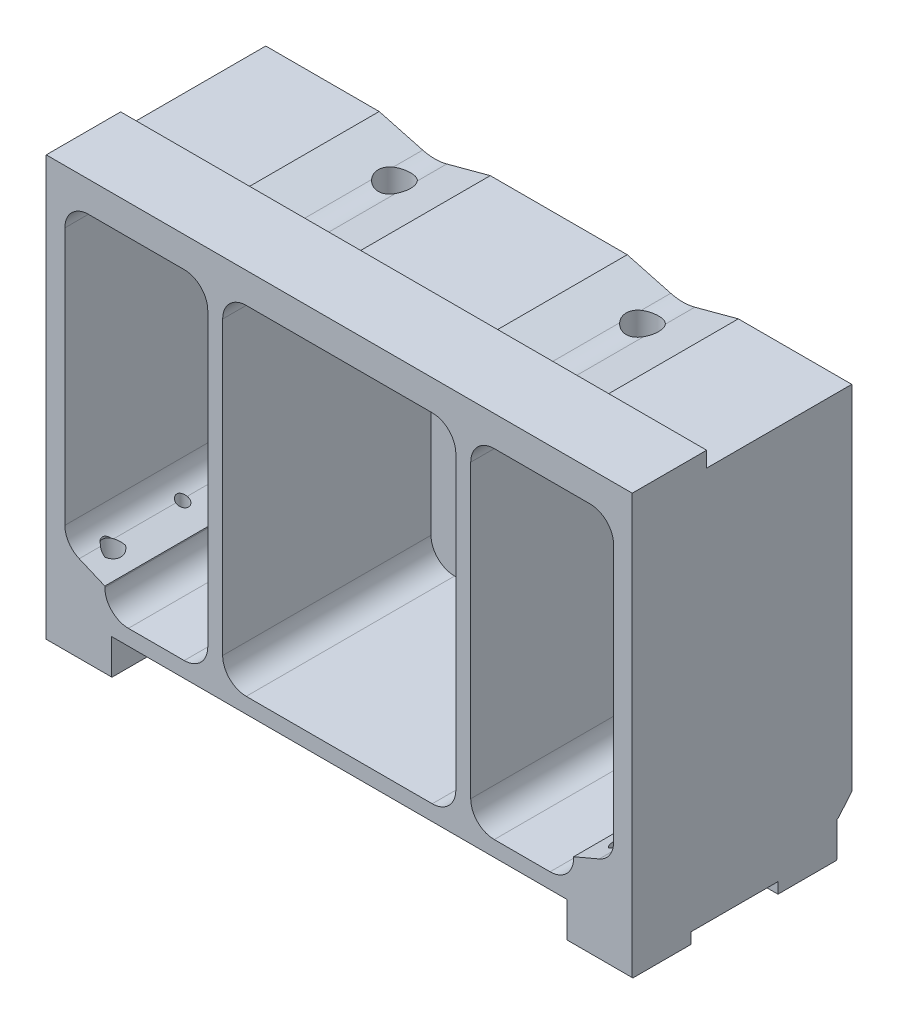
SolidWorks part; units mm, degrees
material "Invar 36"
ref_plane "Front Plane" through (0, 0, 0) normal (0, 0, 1) x (1, 0, 0)
ref_plane "Top Plane" through (0, 0, 0) normal (0, 1, 0) x (1, 0, 0)
ref_plane "Right Plane" through (0, 0, 0) normal (1, 0, 0) x (0, 0, -1)
sketch "Sketch1" plane through (0, 0, 0) normal (0, 0, 1) x (1, 0, 0)
  line L0 (-60.0075, 0) -> (60.0075, 0)
  line L1 (60.0075, 0) -> (60.0075, 82.8802)
  line L2 (60.0075, 82.8802) -> (-60.0075, 82.8802)
  line L4 (-60.0075, 82.8802) -> (-60.0075, 0)
  dimension "D1" = 120.015
  dimension "D2" = 82.8802
extrude "Boss-Extrude1" add sketch "Sketch1" along normal mid plane 41.91
sketch "Sketch3" plane through (0, 0, 0) normal (0, -1, 0) x (1, 0, 0)
  line L0 (-53.0225, -15.24) -> (53.0225, 15.24) construction
  line L1 (-53.0225, 15.24) -> (53.0225, 15.24) construction
  line L2 (-53.0225, 15.24) -> (-53.0225, -15.24) construction
  line L3 (-53.0225, -15.24) -> (53.0225, -15.24) construction
  line L4 (53.0225, 15.24) -> (53.0225, -15.24) construction
  circle A0 centre (-53.0225, 15.24) radius 1.5875
  circle A1 centre (53.0225, 15.24) radius 1.5875
  circle A2 centre (53.0225, -15.24) radius 1.5875
  circle A3 centre (-53.0225, -15.24) radius 1.5875
  dimension "D3" = 3.175
  dimension "D1" = 106.045
  dimension "D2" = 30.48
extrude "Cut-Extrude2" cut sketch "Sketch3" against normal blind 2.54
hole_wizard "Tapped Hole for #10-32 Helicoil1" positions "Sketch4" profile "Sketch5" tap size "#10-32" standard "Helicoil® Inch"
sketch "Sketch4" plane through (0, 0, 0) normal (0, -1, 0) x (1, 0, 0)
  point P0 (-53.0225, 15.24)
  point P3 (-53.0225, -15.24)
  point P6 (53.0225, 15.24)
  point P9 (53.0225, -15.24)
cosmetic thread "Hole Thread1" parameters "D1"=11.5316, "D2"=5.936
cosmetic thread "Hole Thread2" parameters "D1"=11.5316, "D2"=5.936
cosmetic thread "Hole Thread3" parameters "D1"=11.5316, "D2"=5.936
cosmetic thread "Hole Thread4" parameters "D1"=11.5316, "D2"=5.936
sketch "Sketch5" plane through (-53.0225, 0, 15.24) normal (1, 0, 0) x (0, 0, -1)
  line L0 (0, 0) -> (0, 18.628)
  line L1 (0, 18.628) -> (2.5527, 17.0942)
  line L2 (2.5527, 17.0942) -> (2.5527, 0)
  line L5 (2.5527, 0) -> (0, 0)
  line L10 (0, 18.628) -> (-2.5527, 17.0942) construction
  line L11 (0, -6.35) -> (0, 107.95) construction
  dimension "Tap Drill Dia." = 5.1054
  dimension "Tap Drill Depth" = 17.0942
  dimension "Drill Angle" = 118
chamfer "Chamfer1" distance 0.127 angle 45 2 edges at (0, 0, -20.955) (0, 0, 20.955)
sketch "Sketch6" plane through (0, 0, 0) normal (0, -1, 0) x (1, 0, 0)
  line L0 (-60.0075, 20.955) -> (60.0075, 20.955) construction
  line L1 (-46.6725, 20.955) -> (46.6725, 20.955)
  line L2 (-46.6725, 20.955) -> (-46.6725, 8.89)
  line L3 (-46.6725, -20.955) -> (46.6725, -20.955)
  line L4 (46.6725, 20.955) -> (46.6725, 8.89)
  line L5 (60.0075, -20.955) -> (-60.0075, -20.955) construction
  line L6 (-60.0075, 20.828) -> (-60.0075, -20.828) construction
  line L7 (-60.0075, 8.89) -> (-46.6725, 8.89)
  line L8 (-60.0075, 8.89) -> (-60.0075, -8.89)
  line L9 (-60.0075, -8.89) -> (-46.6725, -8.89)
  line L10 (60.0075, 8.89) -> (60.0075, -8.89)
  line L11 (60.0075, 20.828) -> (60.0075, -20.828) construction
  line L12 (-46.6725, -8.89) -> (-46.6725, -20.955)
  line L13 (46.6725, 8.89) -> (60.0075, 8.89)
  line L14 (46.6725, -8.89) -> (60.0075, -8.89)
  line L15 (46.6725, -8.89) -> (46.6725, -20.955)
  circle A0 centre (-53.0225, 15.24) radius 2.5527 construction
  circle A1 centre (53.0225, 15.24) radius 2.5527 construction
  circle A2 centre (-53.0225, -15.24) radius 2.5527 construction
  dimension "D1" = 6.35
  dimension "D3" = 6.35
  dimension "D2" = 6.35
  dimension "D4" = 6.35
extrude "Cut-Extrude3" cut sketch "Sketch6" against normal blind 7.3152
sketch "Sketch7" plane through (0, 7.3152, 0) normal (0, -1, 0) x (1, 0, 0)
  line L0 (-53.0225, 15.24) -> (-53.0225, -15.24) construction
  line L2 (53.0225, 15.24) -> (53.0225, -15.24) construction
  line L4 (-53.0225, 0) -> (53.0225, 0) construction
  circle A0 centre (-53.0225, 0) radius 1.585
  circle A4 centre (53.0225, 0) radius 1.585
  dimension "D1" = 3.1699
extrude "Cut-Extrude4" cut sketch "Sketch7" against normal blind 6.35
sketch "Sketch8" plane through (0, 0, -20.955) normal (0, 0, -1) x (-1, 0, 0)
  line L0 (60.0075, 82.8802) -> (60.0075, 0.127) construction
  line L1 (-60.0075, 82.8802) -> (60.0075, 82.8802)
  line L2 (-60.0075, 82.8802) -> (-60.0075, 7.3152)
  line L3 (-60.0075, 7.3152) -> (60.0075, 7.3152)
  line L4 (60.0075, 82.8802) -> (60.0075, 7.3152)
  line L5 (46.6725, 7.3152) -> (-46.6725, 7.3152) construction
extrude "Boss-Extrude2" add sketch "Sketch8" along normal blind 3.048
chamfer "Chamfer2" distance 2.794 angle 50 1 edges at (0, 7.3152, -24.003) first distance on face at (-53.0225, 7.3152, -1.585)
sketch "Sketch2" plane through (0, 0, 20.955) normal (0, 0, 1) x (1, 0, 0)
  line L0 (60.0075, 82.8802) -> (-60.0075, 82.8802) construction
  line L1 (-43.1815, 66.3702) -> (43.1815, 66.3702)
  line L2 (-48.0075, 61.5442) -> (-48.0075, 58.7502)
  line L3 (-43.1815, 10.4902) -> (43.1815, 10.4902)
  line L4 (48.0075, 61.5442) -> (48.0075, 58.7502)
  line L9 (-60.0075, 82.8802) -> (-60.0075, 0.127) construction
  line L10 (-48.0075, 15.5744) -> (-53.2567, 17.8019)
  line L11 (-56.1975, 22.2444) -> (-56.1975, 51.2354)
  line L12 (46.6725, 7.3152) -> (-46.6725, 7.3152) construction
  line L14 (-53.7845, 55.4148) -> (-48.0075, 58.7502)
  line L15 (-48.0075, 15.5744) -> (-48.0075, 15.3162)
  line L16 (0, 0) -> (0, 54.8538) construction
  line L17 (53.7845, 55.4148) -> (48.0075, 58.7502)
  line L18 (56.1975, 22.2444) -> (56.1975, 51.2354)
  line L19 (48.0075, 15.5744) -> (53.2567, 17.8019)
  line L20 (48.0075, 15.5744) -> (48.0075, 15.3162)
  arc A0 (48.0075, 61.5442) -> (43.1815, 66.3702) centre (43.1815, 61.5442) ccw
  arc A1 (48.0075, 15.3162) -> (43.1815, 10.4902) centre (43.1815, 15.3162) cw
  arc A2 (-43.1815, 10.4902) -> (-48.0075, 15.3162) centre (-43.1815, 15.3162) cw
  arc A3 (-48.0075, 61.5442) -> (-43.1815, 66.3702) centre (-43.1815, 61.5442) cw
  arc A4 (-53.2567, 17.8019) -> (-56.1975, 22.2444) centre (-51.3715, 22.2444) cw
  arc A5 (-56.1975, 51.2354) -> (-53.7845, 55.4148) centre (-51.3715, 51.2354) cw
  arc A6 (56.1975, 51.2354) -> (53.7845, 55.4148) centre (51.3715, 51.2354) ccw
  arc A7 (53.2567, 17.8019) -> (56.1975, 22.2444) centre (51.3715, 22.2444) ccw
  dimension "D5" = 4.826
  dimension "D11" = 4.826
  dimension "D1" = 16.51
  dimension "D2" = 12
  dimension "D3" = 3.175
  dimension "D6" = 3.81
  dimension "D8" = 30
  dimension "D10" = 7.62
extrude "Cut-Extrude1" cut sketch "Sketch2" against normal offset from surface (42.672 mm away) 2.286 up to face at (0, 46.7626, -24.003)
sketch "Sketch9" plane through (0, 0, -24.003) normal (0, 0, -1) x (-1, 0, 0)
  line L0 (-36.7753, 82.8802) -> (-27.8653, 80.4928)
  line L1 (60.0075, 82.8802) -> (-60.0075, 82.8802) construction
  line L2 (-22.9347, 80.4928) -> (-14.0247, 82.8802)
  line L3 (-14.0247, 82.8802) -> (-36.7753, 82.8802)
  line L4 (0, 82.8802) -> (0, 101.334) construction
  line L5 (-25.4, 79.8322) -> (-25.4, 73.1742) construction
  arc A0 (-22.9347, 80.4928) -> (-27.8653, 80.4928) centre (-25.4, 89.6932) cw
  dimension "D5" = 9.525
  dimension "D1" = 15
  dimension "D2" = 15
  dimension "D3" = 25.4
  dimension "D4" = 3.048
extrude "Cut-Extrude5" cut sketch "Sketch9" against normal through all
hole_wizard "Tapped Hole for 1/4-28 Helicoil1" positions "Sketch10" profile "Sketch11" tap size "1/4-28" standard "Helicoil® Inch"
sketch "Sketch10" plane through (0, 82.8802, 0) normal (0, 1, 0) x (1, 0, 0)
  line L0 (36.7753, 24.003) -> (27.8653, 24.003) construction
  point P0 (25.4, 15.748)
  dimension "D1" = 25.4
  dimension "D2" = 8.255
sketch "Sketch11" plane through (25.4, 82.8802, -15.748) normal (1, 0, 0) x (0, 0, 1)
  line L0 (0, 0) -> (0, 23.5817)
  line L1 (0, 23.5817) -> (3.3147, 21.59)
  line L2 (3.3147, 21.59) -> (3.3147, 0)
  line L5 (3.3147, 0) -> (0, 0)
  line L10 (0, 23.5817) -> (-3.3147, 21.59) construction
  line L11 (0, -6.35) -> (0, 107.95) construction
  dimension "Tap Drill Dia." = 6.6294
  dimension "Tap Drill Depth" = 21.59
  dimension "Drill Angle" = 118
cosmetic thread "Hole Thread5" parameters "D1"=14.986, "D2"=7.6073
mirror "Mirror1" about plane through (0, 0, 0) normal (1, 0, 0) of "Tapped Hole for 1/4-28 Helicoil1", "Cut-Extrude5"
cosmetic thread "Hole Thread6" parameters "D1"=14.986, "D2"=7.6073
cosmetic thread "Hole Thread8" parameters "D1"=14.986, "D2"=7.6073
sketch "Sketch12" plane through (0, 0, 20.955) normal (0, 0, 1) x (1, 0, 0)
  line L0 (-18.288, 66.3702) -> (-11.9089, 77.4192)
  line L1 (43.1815, 66.3702) -> (-43.1815, 66.3702) construction
  line L2 (-7.7294, 79.8322) -> (7.7294, 79.8322)
  line L3 (11.9089, 77.4192) -> (18.288, 66.3702)
  line L4 (18.288, 66.3702) -> (-18.288, 66.3702)
  line L5 (0, 82.8802) -> (0, 91.5024) construction
  line L6 (14.0247, 82.8802) -> (-14.0247, 82.8802) construction
  line L7 (-56.1975, 51.2354) -> (-56.1975, 75.0062)
  line L8 (-51.3715, 79.8322) -> (-42.3086, 79.8322)
  line L9 (-38.1291, 77.4192) -> (-31.75, 66.3702)
  line L10 (-48.0075, 61.5442) -> (-48.0075, 58.7502) construction
  line L11 (-48.0075, 58.7502) -> (-53.7845, 55.4148) construction
  line L12 (-43.1815, 66.3702) -> (-31.75, 66.3702)
  line L13 (-48.0075, 61.5442) -> (-48.0075, 58.7502)
  line L14 (-48.0075, 58.7502) -> (-53.7845, 55.4148)
  line L21 (53.7845, 55.4148) -> (48.0075, 58.7502) construction
  line L22 (48.0075, 58.7502) -> (48.0075, 61.5442) construction
  line L23 (53.7845, 55.4148) -> (48.0075, 58.7502)
  line L24 (48.0075, 58.7502) -> (48.0075, 61.5442)
  line L25 (43.1815, 66.3702) -> (31.75, 66.3702)
  line L26 (38.1291, 77.4192) -> (31.75, 66.3702)
  line L27 (56.1975, 51.2354) -> (56.1975, 75.0062)
  line L28 (51.3715, 79.8322) -> (42.3086, 79.8322)
  arc A1 (11.9089, 77.4192) -> (7.7294, 79.8322) centre (7.7294, 75.0062) ccw
  arc A2 (-7.7294, 79.8322) -> (-11.9089, 77.4192) centre (-7.7294, 75.0062) ccw
  arc A3 (-56.1975, 75.0062) -> (-51.3715, 79.8322) centre (-51.3715, 75.0062) cw
  arc A4 (-38.1291, 77.4192) -> (-42.3086, 79.8322) centre (-42.3086, 75.0062) ccw
  arc A5 (-43.1815, 66.3702) -> (-48.0075, 61.5442) centre (-43.1815, 61.5442) ccw construction
  arc A6 (-53.7845, 55.4148) -> (-56.1975, 51.2354) centre (-51.3715, 51.2354) ccw construction
  arc A7 (-43.1815, 66.3702) -> (-48.0075, 61.5442) centre (-43.1815, 61.5442) ccw
  arc A8 (-53.7845, 55.4148) -> (-56.1975, 51.2354) centre (-51.3715, 51.2354) ccw
  arc A12 (56.1975, 51.2354) -> (53.7845, 55.4148) centre (51.3715, 51.2354) ccw construction
  arc A13 (48.0075, 61.5442) -> (43.1815, 66.3702) centre (43.1815, 61.5442) ccw construction
  arc A14 (56.1975, 51.2354) -> (53.7845, 55.4148) centre (51.3715, 51.2354) ccw
  arc A15 (48.0075, 61.5442) -> (43.1815, 66.3702) centre (43.1815, 61.5442) ccw
  arc A16 (38.1291, 77.4192) -> (42.3086, 79.8322) centre (42.3086, 75.0062) cw
  arc A17 (56.1975, 75.0062) -> (51.3715, 79.8322) centre (51.3715, 75.0062) ccw
  dimension "D6" = 4.826
  dimension "D7" = 4.826
  dimension "D10" = 4.826
  dimension "D1" = 18.288
  dimension "D2" = 36.576
  dimension "D3" = 60
  dimension "D4" = 60
  dimension "D5" = 3.048
  dimension "D8" = 31.75
  dimension "D9" = 60
extrude "Cut-Extrude6" cut sketch "Sketch12" against normal up to surface (42.672 mm away) up to face at (0, 37.4623, -21.717)
sketch "Sketch13" plane through (0, 0, 20.955) normal (0, 0, 1) x (1, 0, 0)
  line L0 (-42.3086, 79.8322) -> (42.3086, 79.8322)
  line L1 (42.3086, 79.8322) -> (42.3086, 66.3702)
  line L2 (42.3086, 66.3702) -> (-42.3086, 66.3702)
  line L3 (-42.3086, 66.3702) -> (-42.3086, 79.8322)
  line L4 (-18.288, 66.3702) -> (-31.75, 66.3702) construction
extrude "Cut-Extrude7" cut sketch "Sketch13" against normal blind 29.21
sketch "Sketch14" plane through (0, 82.8802, 0) normal (0, 1, 0) x (1, 0, 0)
  line L0 (60.0075, -20.955) -> (60.0075, 24.003) construction
  line L1 (-60.0075, -20.955) -> (60.0075, -20.955)
  line L2 (-60.0075, -20.955) -> (-60.0075, -5.715)
  line L3 (-60.0075, -5.715) -> (60.0075, -5.715)
  line L4 (60.0075, -20.955) -> (60.0075, -5.715)
  dimension "D1" = 15.24
extrude "Boss-Extrude3" add sketch "Sketch14" against normal up to surface (3.048 mm away) and the other way blind 3.175 up to face at (0, 79.8322, -10.1177)
fillet "Fillet1" radius 2.3876 6 edges at (-32.3203, 81.6865, 5.715) (-25.4, 80.1682, 5.715) (-18.4797, 81.6865, 5.715) (25.4, 80.1682, 5.715) (18.4797, 81.6865, 5.715) (32.3203, 81.6865, 5.715)
sketch "Sketch15" plane through (0, 7.3152, 0) normal (0, -1, 0) x (1, 0, 0)
  line L1 (-60.0075, 8.89) -> (-46.6725, 8.89)
  line L2 (-60.0075, 8.89) -> (-60.0075, -8.89)
  line L3 (-60.0075, -8.89) -> (-46.6725, -8.89)
  line L4 (-46.6725, 8.89) -> (-46.6725, -8.89)
  line L5 (46.6725, 8.89) -> (60.0075, 8.89)
  line L6 (46.6725, 8.89) -> (46.6725, -8.89)
  line L7 (46.6725, -8.89) -> (60.0075, -8.89)
  line L8 (60.0075, 8.89) -> (60.0075, -8.89)
  circle A0 centre (-53.0225, 0) radius 1.585 construction
  circle A1 centre (53.0225, 0) radius 1.585 construction
  circle A2 centre (-53.0225, 0) radius 1.585
  circle A4 centre (53.0225, 0) radius 1.585
extrude "Boss-Extrude4" add sketch "Sketch15" along normal blind 5.08
sketch "Sketch16" plane through (0, 0, -21.717) normal (0, 0, 1) x (1, 0, 0)
  circle A0 centre (0, 40.64) radius 5.1054
  dimension "D1" = 10.2108
  dimension "D2" = 40.64
extrude "Cut-Extrude8" cut sketch "Sketch16" against normal up to next
sketch "Sketch17" plane through (0, 0, 0) normal (0, -1, 0) x (1, 0, 0)
  circle A0 centre (-53.0225, 15.24) radius 1.1938
  circle A1 centre (-53.0225, 0) radius 1.1938
  circle A2 centre (-53.0225, -15.24) radius 1.1938
  circle A3 centre (53.0225, 15.24) radius 1.1938
  circle A4 centre (53.0225, 0) radius 1.1938
  circle A5 centre (53.0225, -15.24) radius 1.1938
  dimension "D1" = 2.3876
extrude "Cut-Extrude9" cut sketch "Sketch17" against normal blind 20.32
ref_plane "Plane2" through (-25.4, 0, 0) normal (1, 0, 0) x (0, 0, -1)
sketch "Sketch19" plane through (-25.4, 0, 0) normal (1, 0, 0) x (0, 0, -1)
  line L0 (-20.955, 79.8322) -> (8.255, 79.8322)
  line L1 (8.255, 79.8322) -> (8.255, 66.3702)
  line L2 (8.255, 66.3702) -> (21.717, 66.3702)
  line L3 (21.717, 66.3702) -> (21.717, 10.4902)
  line L4 (21.717, 10.4902) -> (-20.955, 10.4902)
  line L5 (-20.955, 22.2444) -> (-20.955, 75.0062) construction
  line L6 (-20.955, 10.4902) -> (-20.955, 79.8322)
  line L8 (-20.955, 0.127) -> (-20.955, 86.0552) construction
  line L9 (8.255, 77.4192) -> (8.255, 66.3702) construction
  line L10 (21.717, 79.8322) -> (-20.955, 79.8322) construction
  line L11 (21.717, 66.3702) -> (8.255, 66.3702) construction
  line L12 (21.717, 22.2444) -> (21.717, 75.0062) construction
  line L13 (21.717, 10.4902) -> (-20.955, 10.4902) construction
extrude "Boss-Extrude6" add sketch "Sketch19" along normal mid plane 3.048
pattern_linear "LPattern1" count 2 spacing 50.8 along (1, 0, 0) of "Boss-Extrude6"
fillet "Fillet2" radius 4.826 8 edges at (26.924, 79.8322, 6.35) (23.876, 79.8322, 6.35) (-26.924, 79.8322, 6.35) (-23.876, 79.8322, 6.35) (-23.876, 10.4902, -0.381) (26.924, 10.4902, -0.381) (23.876, 10.4902, -0.381) (-26.924, 10.4902, -0.381)
sketch "Sketch20" plane through (-25.4, 0, 0) normal (1, 0, 0) x (0, 0, -1)
  line L0 (19.0627, 71.6409) -> (19.0627, 61.0838)
  line L1 (19.0627, 61.0838) -> (15.748, 59.0921)
  line L2 (15.748, 66.3702) -> (15.748, 80.4928) construction
  line L3 (15.748, 59.0921) -> (15.748, 71.6409)
  line L4 (15.748, 71.6409) -> (19.0627, 71.6409)
  dimension "D1" = 59
  dimension "D2" = 3.3147
revolve "Cut-Revolve1" cut sketch "Sketch20" angle 360 about L3
pattern_linear "LPattern2" count 2 spacing 50.8 along (1, 0, 0) of "Cut-Revolve1"
cosmetic thread "Hole Thread7" parameters "D1"=14.986, "D2"=7.6073
cosmetic thread "Hole Thread9" parameters "D1"=14.986, "D2"=7.6073
